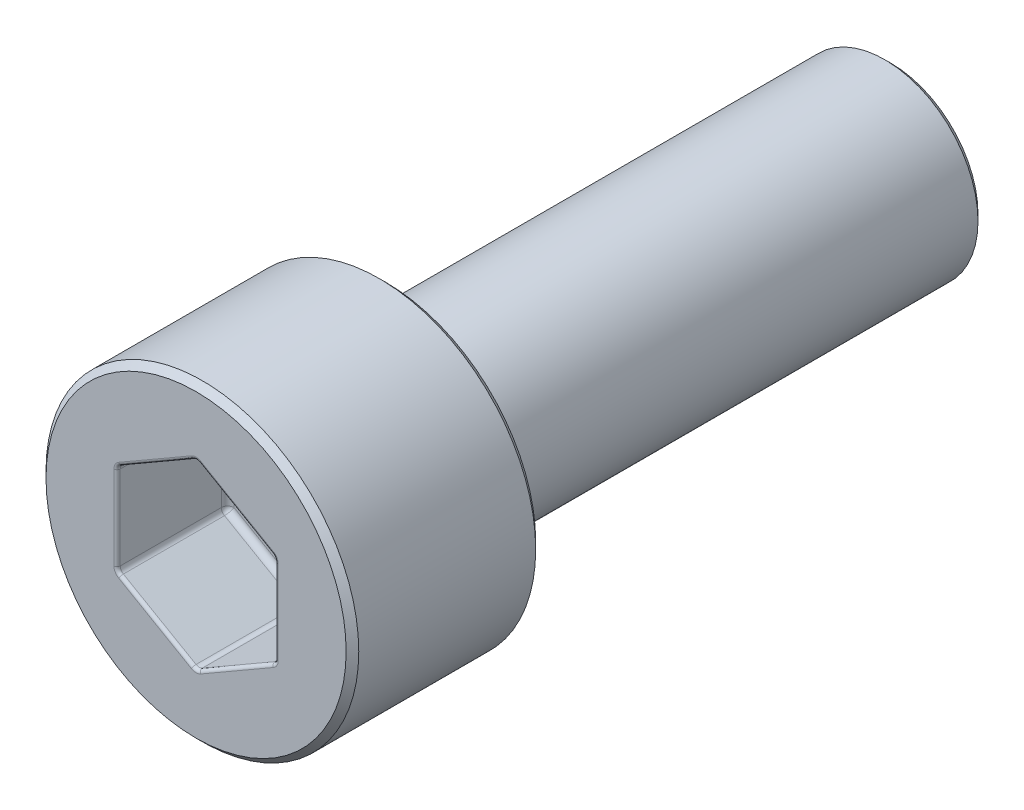
SolidWorks part; units mm, degrees
material "1.4000 (X6Cr13)"
ref_plane "Ebene vorne" through (0, 0, 0) normal (0, 0, 1) x (1, 0, 0)
ref_plane "Ebene oben" through (0, 0, 0) normal (0, 1, 0) x (1, 0, 0)
ref_plane "Ebene rechts" through (0, 0, 0) normal (1, 0, 0) x (0, 0, -1)
sketch "Skizze1" plane through (0, 0, 0) normal (1, 0, 0) x (0, 0, -1)
  line L0 (-21.9199, 0) -> (33.7608, 0) construction
  line L1 (0, 13.9907) -> (0, -9.4798) construction
  line L2 (-6, 0) -> (-6, 4.95)
  line L3 (-6, 4.95) -> (0, 4.95)
  line L4 (0, 4.95) -> (0, 2.95)
  line L5 (0, 2.95) -> (16, 2.95)
  line L6 (16, 2.95) -> (16, 0)
  line L7 (16, 0) -> (-6, 0)
  dimension "D1" = 5.9
  dimension "D2" = 6
  dimension "D3" = 9.9
  dimension "D4" = 16
revolve "Rotation1" add sketch "Skizze1" angle 360 about L0
sketch "Skizze2" plane through (0, 0, 6) normal (0, 0, 1) x (1, 0, 0)
  line L0 (0, 8.6995) -> (0, -7.3778) construction
  line L1 (2.5, -1.4434) -> (2.5, 1.4434)
  line L2 (2.5, 1.4434) -> (0, 2.8868)
  line L3 (0, 2.8868) -> (-2.5, 1.4434)
  line L4 (-2.5, 1.4434) -> (-2.5, -1.4434)
  line L5 (-2.5, -1.4434) -> (0, -2.8868)
  line L6 (0, -2.8868) -> (2.5, -1.4434)
  circle A0 centre (0, 0) radius 2.5 construction
  dimension "D1" = 5
extrude "Schnitt-Linear austragen1" cut sketch "Skizze2" against normal blind 3.5
chamfer "Fase1" distance 0.2 angle 45 3 edges at (4.95, 0, 6) (4.95, 0, 0) (2.95, 0, -16)
fillet "Verrundung1" radius 0.2 13 edges at (-1.25, -2.1651, 2.5) (-2.5, 0, 2.5) (-1.25, 2.1651, 2.5) (1.25, 2.1651, 2.5) (2.5, 0, 2.5) (1.25, -2.1651, 2.5) (-2.5, -1.4434, 4.25) (0, -2.8868, 4.25) (2.5, -1.4434, 4.25) (2.5, 1.4434, 4.25) (0, 2.8868, 4.25) (-2.5, 1.4434, 4.25) (2.95, 0, 0)
fillet "Verrundung2" radius 0.1 12 edges at (2.4732, -1.4279, 6) (1.25, -2.1651, 6) (0, -2.8558, 6) (-1.25, -2.1651, 6) (-2.4732, -1.4279, 6) (-2.5, 0, 6) (-2.4732, 1.4279, 6) (-1.25, 2.1651, 6) (0, 2.8558, 6) (1.25, 2.1651, 6) (2.4732, 1.4279, 6) (2.5, 0, 6)
ref_axis "Achse1" through (0, 0, -19.6323) along (0, 0, 1)
